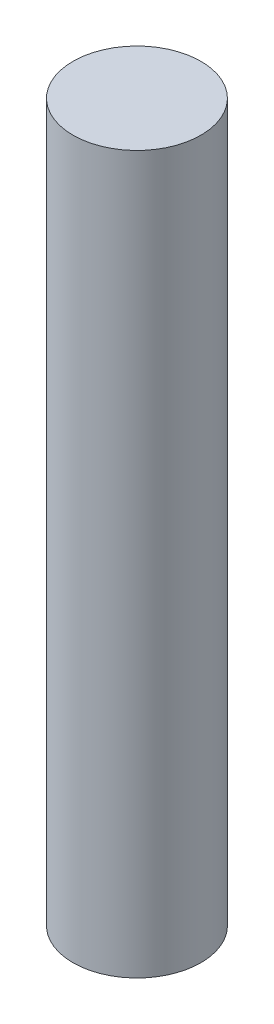
SolidWorks part; units mm, degrees
ref_plane "Front Plane" through (0, 0, 0) normal (0, 0, 1) x (1, 0, 0)
ref_plane "Top Plane" through (0, 0, 0) normal (0, 1, 0) x (1, 0, 0)
ref_plane "Right Plane" through (0, 0, 0) normal (1, 0, 0) x (0, 0, -1)
sketch "Sketch1" plane through (0, 0, 0) normal (0, 1, 0) x (1, 0, 0)
  circle A0 centre (0, 0) radius 2.5
  dimension "D1" = 5
extrude "Boss-Extrude1" add sketch "Sketch1" along normal blind 28
